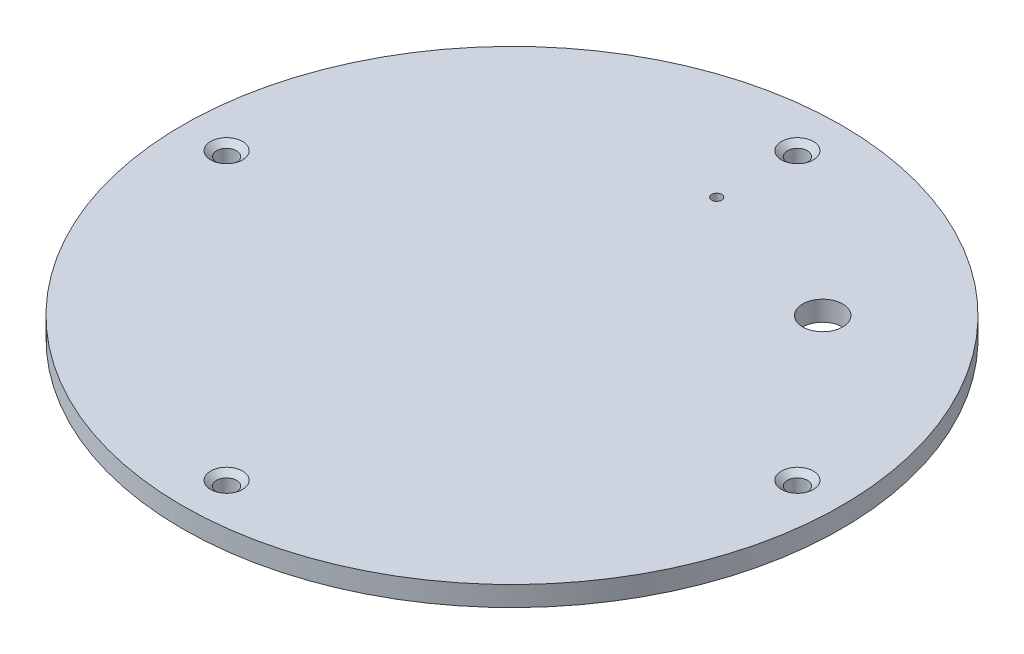
SolidWorks part; units mm, degrees
material "1060 Alloy"
ref_plane "Front Plane" through (0, 0, 0) normal (0, 0, 1) x (1, 0, 0)
ref_plane "Top Plane" through (0, 0, 0) normal (0, 1, 0) x (1, 0, 0)
ref_plane "Right Plane" through (0, 0, 0) normal (1, 0, 0) x (0, 0, -1)
sketch "Sketch1" plane through (0, 0, 0) normal (0, 1, 0) x (1, 0, 0)
  circle A0 centre (0, 0) radius 16.5
  dimension "D1" = 33
extrude "Boss-Extrude1" add sketch "Sketch1" along normal blind 1
hole_wizard "CSK for M2 Flat Head Machine Screw1" positions "Sketch2" profile "Sketch3" countersink size "M2" standard "ANSI Metric" end condition through all
sketch "Sketch2" plane through (0, 1, 0) normal (0, 1, 0) x (1, 0, 0)
  point P0 (0, 14.29)
  point P2 (14.29, 0)
  point P4 (0, -14.29)
  point P6 (-14.29, 0)
  dimension "D1" = 14.29
  dimension "D2" = 14.29
  dimension "D3" = 14.29
  dimension "D4" = 14.29
sketch "Sketch3" plane through (0, 1, -14.29) normal (1, 0, 0) x (0, 0, 1)
  line L0 (0, 0) -> (0, 1)
  line L1 (0, 1) -> (0.5, 1)
  line L2 (0.5, 1) -> (0.5, 0.2517)
  line L3 (0.5, 0.2517) -> (0.8, 0)
  line L5 (0.8, 0) -> (0, 0)
  line L6 (-0.5, 0.2517) -> (-0.8, 0) construction
  line L11 (0, -6.35) -> (0, 107.95) construction
  dimension "Thru Hole Dia." = 1
  dimension "Thru Hole Depth" = 1
  dimension "Near C'Sink Dia." = 1.6
  dimension "Near C'Sink Angle" = 100
sketch "Sketch5" plane through (0, 1, 0) normal (0, 1, 0) x (1, 0, 0)
  line L0 (0, 0) -> (12.6106, 12.6106) construction
  line L1 (0, 0) -> (20.4022, 0) construction
  circle A0 centre (0, 10.25) radius 0.25
  circle A1 centre (7.7782, 7.7782) radius 1
  dimension "D1" = 0.5
  dimension "D2" = 10.25
  dimension "D3" = 2
  dimension "D4" = 11
  dimension "D5" = 45
extrude "Cut-Extrude1" cut sketch "Sketch5" against normal through all both and the other way through all
